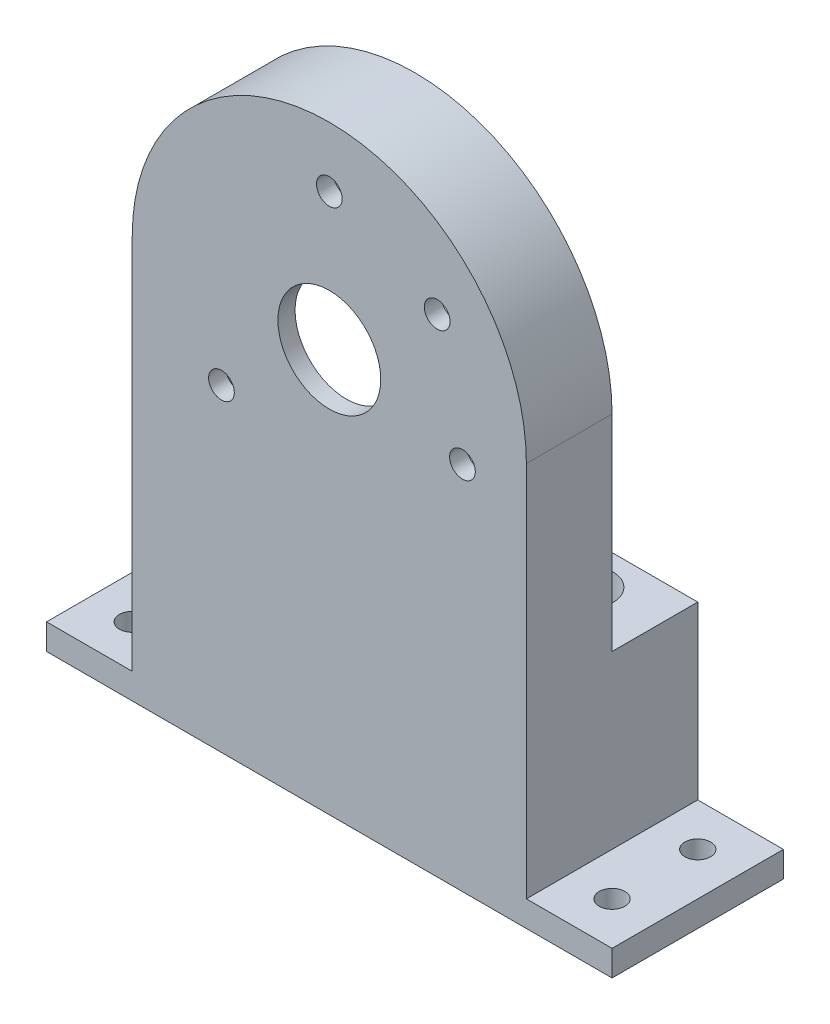
SolidWorks part; units mm, degrees
ref_plane "前视基准面" through (0, 0, 0) normal (0, 0, 1) x (1, 0, 0)
ref_plane "上视基准面" through (0, 0, 0) normal (0, 1, 0) x (1, 0, 0)
ref_plane "右视基准面" through (0, 0, 0) normal (1, 0, 0) x (0, 0, -1)
other "Configuration Table"
sketch "草图1" plane through (0, 0, 0) normal (0, 0, 1) x (1, 0, 0)
  line L0 (-23, 0) -> (-23, -27)
  line L1 (-23, -27) -> (23, -27)
  line L2 (23, -27) -> (23, 0)
  arc A1 (23, 0) -> (-23, 0) centre (0, 0) ccw
  dimension "D1" = 27
  dimension "D2" = 23
extrude "凸台-拉伸1" add sketch "草图1" along normal blind 20
sketch "草图2" plane through (0, 0, 0) normal (0, 0, -1) x (-1, 0, 0)
  line L0 (-23, -24) -> (23, -24)
  line L1 (23, 0) -> (23, -27) construction
  line L2 (-23, -27) -> (-23, 0) construction
  line L3 (-23, 0) -> (-23, -27)
  line L4 (-23, -27) -> (23, -27)
  line L5 (23, -27) -> (23, 0)
  line L6 (-23, 0) -> (-23, -24)
  line L8 (23, -24) -> (23, 0)
  arc A1 (23, 0) -> (-23, 0) centre (0, 0) ccw
  arc A2 (23, 0) -> (-23, 0) centre (0, 0) ccw
  dimension "D2" = 24
  dimension "D1" = 0
extrude "切除-拉伸1" cut sketch "草图2" against normal blind 10
sketch "草图3" plane through (0, 0, 10) normal (0, 0, -1) x (-1, 0, 0)
  circle A0 centre (0, 0) radius 21
extrude "切除-拉伸2" cut sketch "草图3" against normal blind 8
sketch "草图7" plane through (0, 0, 20) normal (0, 0, 1) x (1, 0, 0)
  circle A0 centre (0, 16) radius 1.5 construction
  circle A1 centre (0, 16) radius 1.5
  circle A2 centre (12.5891, 9.875) radius 1.5 construction
  circle A3 centre (12.5891, 9.875) radius 1.5
  circle A4 centre (-12.5891, -9.875) radius 1.5 construction
  circle A5 centre (15.5396, -3.8105) radius 1.5 construction
  circle A6 centre (-12.5891, -9.875) radius 1.5
  circle A7 centre (15.5396, -3.8105) radius 1.5
extrude "切除-拉伸6" cut sketch "草图7" against normal blind 3
sketch "草图8" plane through (0, 0, 18) normal (0, 0, -1) x (-1, 0, 0)
  circle A1 centre (0, 0) radius 6
  circle A2 centre (0, 0) radius 6
  dimension "D1" = 0
extrude "切除-拉伸7" cut sketch "草图8" against normal blind 3
sketch "草图12" plane through (0, -27, 0) normal (0, -1, 0) x (1, 0, 0)
  line L4 (-23, 0) -> (23, 0)
  line L5 (23, 0) -> (23, 20)
  line L6 (23, 20) -> (-23, 20)
  line L7 (-23, 20) -> (-23, 0)
  line L8 (-23, 0) -> (23, 0)
  line L9 (23, 0) -> (23, 20)
  line L10 (23, 20) -> (-23, 20)
  line L11 (-23, 20) -> (-23, 0)
  dimension "D1" = 0
extrude "凸台-拉伸4" add sketch "草图12" along normal blind 20
sketch "草图13" plane through (0, -24, 0) normal (0, 1, 0) x (1, 0, 0)
  line L0 (19.5, -5) -> (-24.0032, -5) construction
  line L1 (23, -10) -> (23, 0) construction
  line L2 (0, -11) -> (0, 11) construction
  circle A0 centre (15, -5) radius 3.1
  circle A1 centre (-15, -5) radius 3.1
  point P5 (15.0287, -5)
  dimension "D1" = 8
extrude "切除-拉伸8" cut sketch "草图13" against normal blind 20
sketch "草图14" plane through (0, -47, 0) normal (0, -1, 0) x (1, 0, 0)
  line L0 (23, 20) -> (33, 20)
  line L1 (-33, 20) -> (-23, 20)
  line L2 (-33, 20) -> (-33, 0)
  line L3 (-33, 0) -> (-23, 0)
  line L4 (33, 20) -> (33, 0)
  line L6 (-23, 20) -> (-23, 0)
  line L8 (23, 20) -> (23, 0)
  line L9 (23, 0) -> (33, 0)
  circle A0 centre (28, 5) radius 1.5
  circle A1 centre (28, 15) radius 1.5
  circle A2 centre (-28, 5) radius 1.5
  circle A3 centre (-28, 15) radius 1.5
extrude "凸台-拉伸5" add sketch "草图14" against normal blind 3
sketch "草图15" plane through (0, -44, 0) normal (0, 1, 0) x (1, 0, 0)
  circle A0 centre (-15, -5) radius 1.5
  circle A1 centre (15, -5) radius 1.5
extrude "切除-拉伸9" cut sketch "草图15" against normal through all
